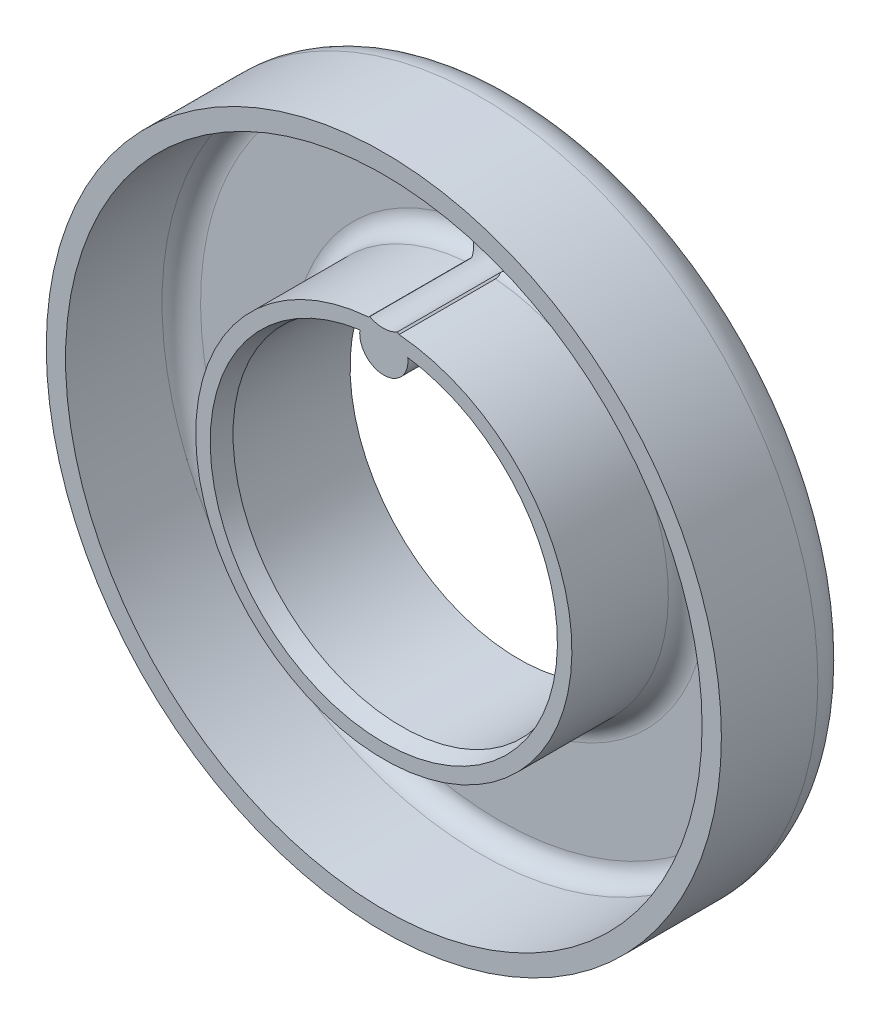
SolidWorks part; units mm, degrees
ref_plane "Alzado" through (0, 0, 0) normal (0, 0, 1) x (1, 0, 0)
ref_plane "Planta" through (0, 0, 0) normal (0, 1, 0) x (1, 0, 0)
ref_plane "Vista lateral" through (0, 0, 0) normal (1, 0, 0) x (0, 0, -1)
sketch "Croquis1" plane through (0, 0, 0) normal (0, 0, 1) x (1, 0, 0)
  circle A0 centre (0, 0) radius 35
  dimension "D1" = 70
extrude "Saliente-Extruir1" add sketch "Croquis1" along normal blind 14
sketch "Croquis2" plane through (0, 0, 14) normal (0, 0, 1) x (1, 0, 0)
  circle A0 centre (0, 0) radius 17.5
  dimension "D1" = 35
extrude "Cortar-Extruir1" cut sketch "Croquis2" against normal through all
shell "Vaciado1" thickness 2 removed face at (17.5, 0, 14)
chamfer "Chaflán1" distance 0.5 angle 75 1 edges at (17.5, 0, 14) first distance on face at (17.5, 0, 14)
sketch "Croquis5" plane through (0, 0, 0) normal (0, 0, -1) x (-1, 0, 0)
  circle A0 centre (0, 17.5) radius 2.5
  circle A1 centre (0, 0) radius 17.5 construction
  dimension "D1" = 5
extrude "Saliente-Extruir2" add sketch "Croquis5" against normal through all
fillet "Redondeo1" radius 2 2 edges at (0, -19.5, 2) (33, 0, 2)
fillet "Redondeo2" radius 4 1 edges at (35, 0, 0)
sketch "Croquis3" plane through (0, 0, 2) normal (0, 0, 1) x (1, 0, 0)
  line L1 (6.2887, 28.5535) -> (-0.0753, 22.1895) construction
  line L2 (8.41, 26.4322) -> (2.0461, 20.0682)
  line L4 (4.1674, 30.6748) -> (-2.1966, 24.3109)
  arc A0 (8.41, 26.4322) -> (4.1674, 30.6748) centre (6.2887, 28.5535) ccw
  arc A1 (-2.1966, 24.3109) -> (2.0461, 20.0682) centre (-0.0753, 22.1895) ccw
  point P4 (3.1067, 25.3715)
  dimension "D3" = 3
  dimension "D2" = 9
extrude "Cortar-Extruir2" cut sketch "Croquis3" against normal through all and the other way through all
sketch "Croquis4" plane through (0, 0, 2) normal (0, 0, 1) x (1, 0, 0)
  line L0 (5.0896, 21.6514) -> (4.628, 20.2264)
  line L1 (4.628, 20.2264) -> (6.3189, 19.6786)
  line L2 (6.3189, 19.6786) -> (6.0819, 18.9471)
  line L3 (6.0819, 18.9471) -> (7.9937, 19.9234)
  line L4 (7.9937, 19.9234) -> (7.0175, 21.8352)
  line L5 (7.0175, 21.8352) -> (6.7805, 21.1037)
  line L6 (6.7805, 21.1037) -> (5.0896, 21.6514)
extrude "Cortar-Extruir3" cut sketch "Croquis4" against normal through all and the other way through all
